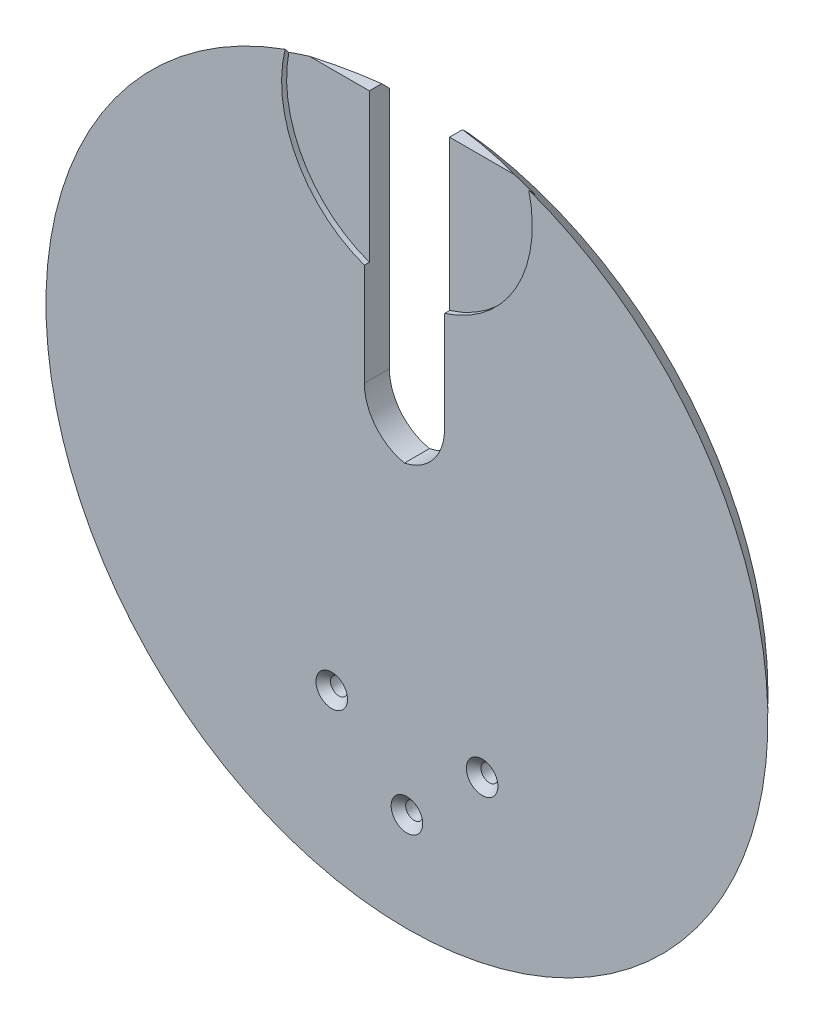
SolidWorks part; units mm, degrees
material "PET"
ref_plane "Front Plane" through (0, 0, 0) normal (0, 0, 1) x (1, 0, 0)
ref_plane "Top Plane" through (0, 0, 0) normal (0, 1, 0) x (1, 0, 0)
ref_plane "Right Plane" through (0, 0, 0) normal (1, 0, 0) x (0, 0, -1)
sketch "Sketch1" plane through (0, 0, 0) normal (0, 0, 1) x (1, 0, 0)
  line L0 (-9.944, -71.31) -> (9.944, -71.31) construction
  line L1 (-66.4124, -27.81) -> (66.4124, -27.81) construction
  line L2 (-35.1981, -62.81) -> (35.1981, -62.81) construction
  line L3 (0, -27.81) -> (0, -62.81) construction
  line L4 (-23.6643, 68) -> (23.6643, 68)
  arc A0 (-23.6643, 68) -> (23.6643, 68) centre (0, 0) ccw
  circle A1 centre (0, -52.31) radius 2.397 construction
  circle A2 centre (-15, -38.31) radius 2.5305 construction
  circle A3 centre (15, -38.31) radius 2.5603 construction
  arc A4 (23.6643, 68) -> (-23.6643, 68) centre (0, 0) ccw construction
  point P13 (0, -45.31)
  dimension "D1" = 144
  dimension "D2" = 71.31
  dimension "D3" = 43.5
  dimension "D4" = 35
  dimension "D5" = 7
  dimension "D6" = 15
  dimension "D7" = 15
  dimension "D8" = 7
  dimension "D9" = 68
extrude "Boss-Extrude2" add sketch "Sketch1" along normal blind 5 contours A0 L4
chamfer "Chamfer1" distance 5 angle 45 1 edges at (0, -72, 0)
sketch "Sketch2" plane through (0, 0, 5) normal (0, 0, 1) x (1, 0, 0)
  point P0 (15, -38.31)
  point P3 (-15, -38.31)
  point P6 (0, -52.31)
hole_wizard "CSK for M3 Countersunk Flat Head Screw1" positions "Sketch2" profile "Sketch3" countersink size "M3" standard "ISO"
sketch "Sketch3" plane through (15, -38.31, 5) normal (1, 0, 0) x (0, -1, 0)
  line L0 (0, 0) -> (0, 6.0215)
  line L1 (0, 6.0215) -> (1.7, 5)
  line L2 (1.7, 5) -> (1.7, 1.45)
  line L3 (1.7, 1.45) -> (3.15, 0)
  line L5 (3.15, 0) -> (0, 0)
  line L6 (-1.7, 1.45) -> (-3.15, 0) construction
  line L10 (0, 6.0215) -> (-1.7, 5) construction
  line L11 (0, -6.35) -> (0, 107.95) construction
  dimension "Hole Dia." = 3.4
  dimension "Hole Depth" = 5
  dimension "Near C'Sink Dia." = 6.3
  dimension "Near C'Sink Angle" = 90
  dimension "Drill Angle" = 118
sketch "Sketch4" plane through (0, 0, 5) normal (0, 0, 1) x (1, 0, 0)
  line L5 (23.6643, 68) -> (-23.6643, 68)
  line L6 (23.6643, 68) -> (-23.6643, 68)
  line L7 (-8.5, 8) -> (7.5, 8)
  line L8 (-8.5, 8) -> (-8.5, 68)
  line L9 (-8.5, 68) -> (7.5, 68)
  line L10 (7.5, 8) -> (7.5, 68)
  arc A2 (-23.6643, 68) -> (23.6643, 68) centre (0, 0) ccw
  arc A3 (-23.6643, 68) -> (23.6643, 68) centre (0, 0) ccw
  dimension "D1" = 60
  dimension "D2" = 7.5
  dimension "D3" = 16
  dimension "D4" = 0
extrude "Cut-Extrude1" cut sketch "Sketch4" against normal up to surface (5 mm away) contours L7 L10 L6 L8 region at (-0.5, 38, 5) up to face at (-13.3, -38.31, 0)
sketch "Sketch5" plane through (0, 0, 5) normal (0, 0, 1) x (1, 0, 0)
  circle A0 centre (0, 61.9) radius 25
  dimension "D1" = 50
  dimension "D2" = 61.9
extrude "Cut-Extrude2" cut sketch "Sketch5" against normal blind 1
fillet "Fillet1" radius 10 2 edges at (-8.5, 8, 2.5) (7.5, 8, 2.5)
